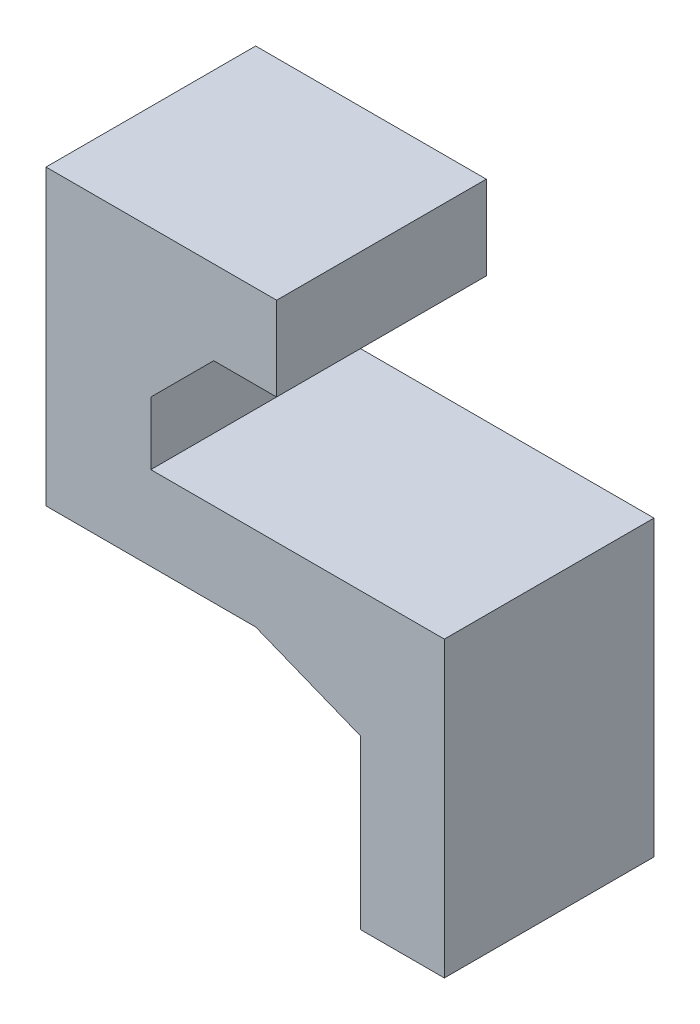
SolidWorks part; units mm, degrees
ref_plane "Plan de face" through (0, 0, 0) normal (0, 0, 1) x (1, 0, 0)
ref_plane "Plan de dessus" through (0, 0, 0) normal (0, 1, 0) x (1, 0, 0)
ref_plane "Plan de droite" through (0, 0, 0) normal (1, 0, 0) x (0, 0, -1)
sketch "Esquisse1" plane through (0, 0, 0) normal (0, 0, 1) x (1, 0, 0)
  line L0 (-40, 100) -> (-70, 100)
  line L1 (-70, 100) -> (-70, 70)
  line L2 (-70, 70) -> (0, 70)
  line L3 (0, 70) -> (0, 0)
  line L4 (0, 0) -> (-20, 0)
  line L5 (-20, 0) -> (-20, 50)
  line L6 (-20, 50) -> (-95, 50)
  line L7 (-95, 50) -> (-95, 120)
  line L8 (-95, 120) -> (-40, 120)
  line L9 (-40, 120) -> (-40, 100)
  dimension "D1" = 20
  dimension "D2" = 20
  dimension "D3" = 30
  dimension "D4" = 70
  dimension "D5" = 50
  dimension "D6" = 55
  dimension "D7" = 70
  dimension "D8" = 75
extrude "Boss.-Extru.1" add sketch "Esquisse1" against normal blind 50 contours L0 L1 L2 L3 L4 L5 L6 L7 L8 L9
sketch "Esquisse3" plane through (0, 0, 0) normal (0, 0, 1) x (1, 0, 0)
  line L0 (-45, 50) -> (-20, 40)
  line L1 (-20, 50) -> (-95, 50) construction
  line L2 (-20, 0) -> (-20, 50) construction
  line L3 (-45, 50) -> (-20, 50)
  line L5 (-70, 85) -> (-55, 100)
  line L7 (-20, 50) -> (-20, 40)
  line L8 (-70, 100) -> (-70, 70) construction
  line L9 (-40, 100) -> (-70, 100) construction
  line L10 (-55, 100) -> (-70, 100)
  line L11 (-70, 100) -> (-70, 85)
  line L12 (-70, 85) -> (-70.1708, 84.9063)
  line M9 (-70, 70) -> (-70, 100)
  line M10 (-70, 100) -> (-40, 100)
  dimension "D1" = 15
  dimension "D2" = 15
  dimension "D3" = 25
  dimension "D4" = 40
extrude "Boss.-Extru.2" add sketch "Esquisse3" against normal blind 50 contours L0 L7 L3
extrude "Boss.-Extru.3" add sketch "Esquisse3<4>" against normal blind 50 contours L5 M9 M10 region at (-65, 95, 0)
sketch "Esquisse3<4>" plane through (0, 0, 0) normal (0, 0, 1) x (1, 0, 0) same geometry as "Esquisse3"
